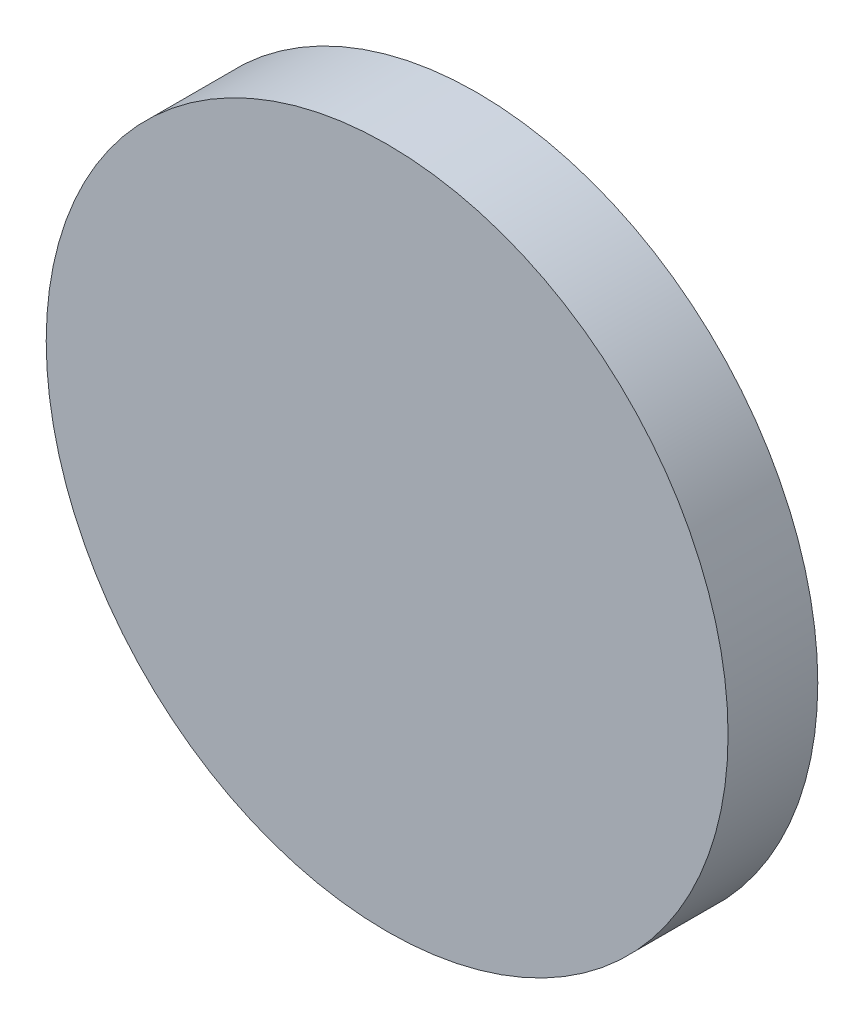
SolidWorks part; units mm, degrees
ref_plane "Front Plane" through (0, 0, 0) normal (0, 0, 1) x (1, 0, 0)
ref_plane "Top Plane" through (0, 0, 0) normal (0, 1, 0) x (1, 0, 0)
ref_plane "Right Plane" through (0, 0, 0) normal (1, 0, 0) x (0, 0, -1)
sketch "Sketch1" plane through (0, 0, 0) normal (0, 0, 1) x (1, 0, 0)
  line L0 (0, 10.3237) -> (0, -11.9962) construction
  circle A0 centre (0, 0) radius 19
  circle A1 centre (0, 0) radius 2 construction
  dimension "D1" = 4
  dimension "D2" = 38
extrude "Boss-Extrude1" add sketch "Sketch1" along normal blind 5
sketch "Sketch3" plane through (0, 0, 0) normal (0, 1, 0) x (1, 0, 0)
  line L0 (-14.5, 6.5) -> (-14.5, 0) construction
  line L1 (19, 0) -> (-19, 0) construction
  line L2 (-16.5, 6.5) -> (-16.5, 0)
  line L3 (-16.5, 0) -> (-14.5, 0)
  line L4 (-14.5, 0) -> (-14.5, 8.5)
  line L5 (-19, 0) -> (-19, -5) construction
  circle A0 centre (-14.5, 6.5) radius 2 construction
  arc A1 (-16.5, 6.5) -> (-14.5, 8.5) centre (-14.5, 6.5) cw
  dimension "D1" = 4
  dimension "D2" = 4.5
  dimension "D3" = 8.5
revolve "Revolve1" add sketch "Sketch3" angle 360 about L0
